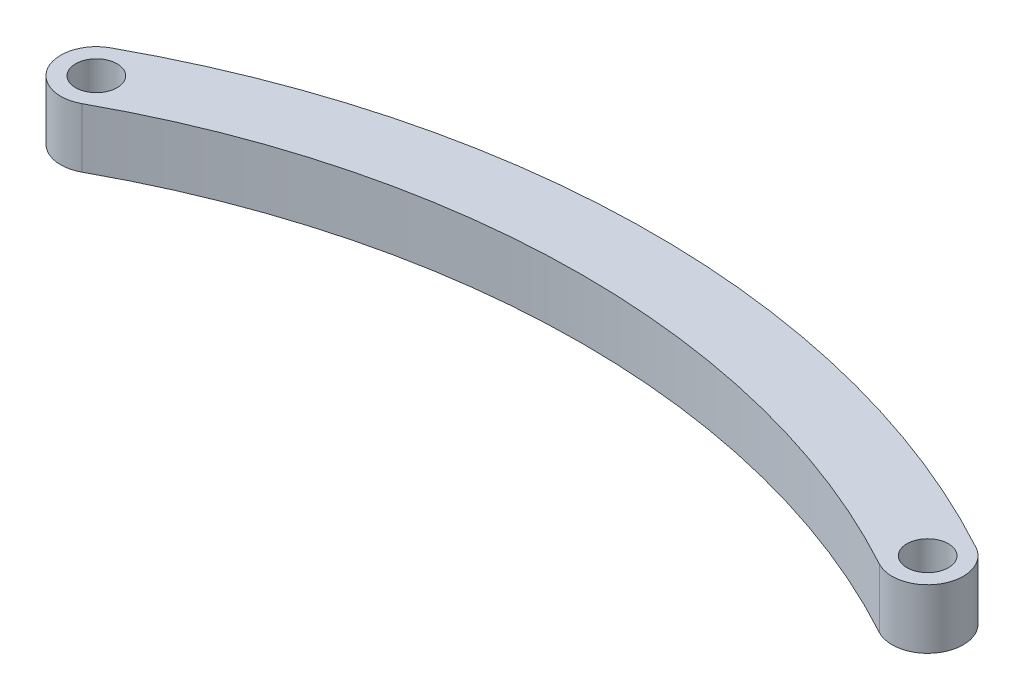
SolidWorks part; units mm, degrees
ref_plane "Front Plane" through (0, 0, 0) normal (0, 0, 1) x (1, 0, 0)
ref_plane "Top Plane" through (0, 0, 0) normal (0, 1, 0) x (1, 0, 0)
ref_plane "Right Plane" through (0, 0, 0) normal (1, 0, 0) x (0, 0, -1)
sketch "Esquisse1" plane through (0, 0, 0) normal (0, 1, 0) x (1, 0, 0)
  line L0 (-35, 0) -> (0, 0) construction
  line L1 (0, 0) -> (35, 0) construction
  circle A0 centre (-35, 0) radius 1.75
  circle A1 centre (35, 0) radius 1.75
  circle A2 centre (-35, 0) radius 3
  circle A3 centre (35, 0) radius 3
  circle A4 centre (0, -64.0625) radius 70
  circle A5 centre (0, -64.0625) radius 76
  dimension "D2" = 3.5
  dimension "D3" = 6
  dimension "D4" = 140
  dimension "D5" = 152
  dimension "D1" = 35
extrude "Boss.-Extru.1" add sketch "Esquisse1" along normal blind 5 contours A3 A5 A2 A4 | A2 A0 | A3 A1 region at (-32.4928, 0, 1.4872) region at (0, 0, -6.3427) region at (37.5072, 0, -1.4872)
